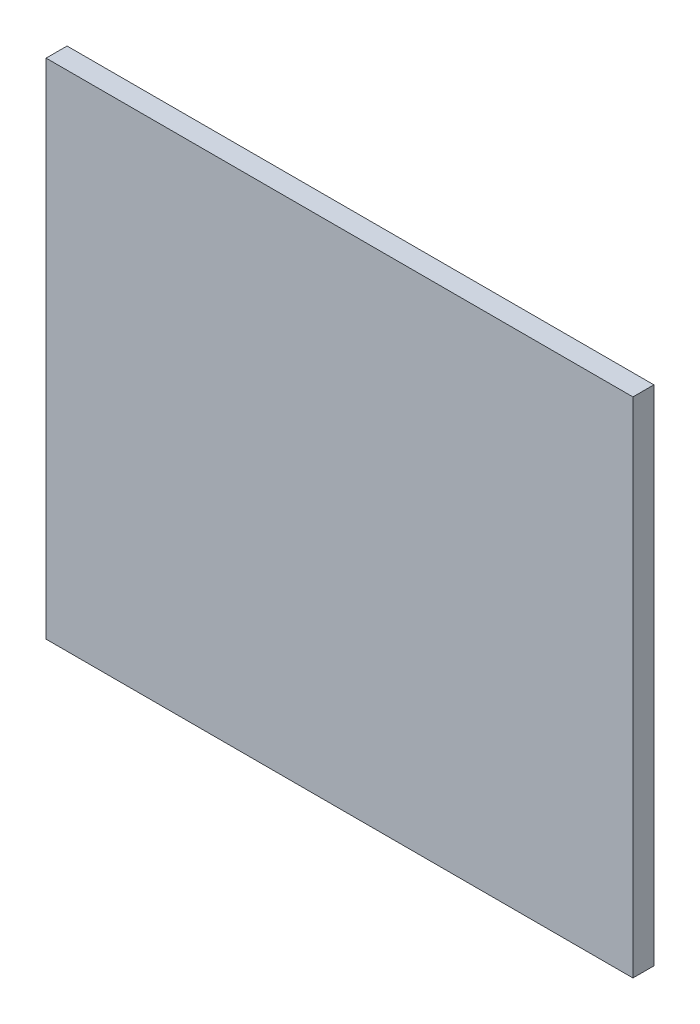
SolidWorks part; units mm, degrees
ref_plane "Front Plane" through (0, 0, 0) normal (0, 0, 1) x (1, 0, 0)
ref_plane "Top Plane" through (0, 0, 0) normal (0, 1, 0) x (1, 0, 0)
ref_plane "Right Plane" through (0, 0, 0) normal (1, 0, 0) x (0, 0, -1)
sketch "Sketch1" plane through (0, 0, 0) normal (0, 0, 1) x (1, 0, 0)
  line L1 (-266.573, 2683.51) -> (266.573, 2683.51)
  line L2 (-266.573, 2683.51) -> (-266.573, 3140.71)
  line L3 (-266.573, 3140.71) -> (266.573, 3140.71)
  line L4 (266.573, 2683.51) -> (266.573, 3140.71)
  dimension "D1" = 457.2
extrude "Boss-Extrude1" add sketch "Sketch1" against normal blind 19.05
